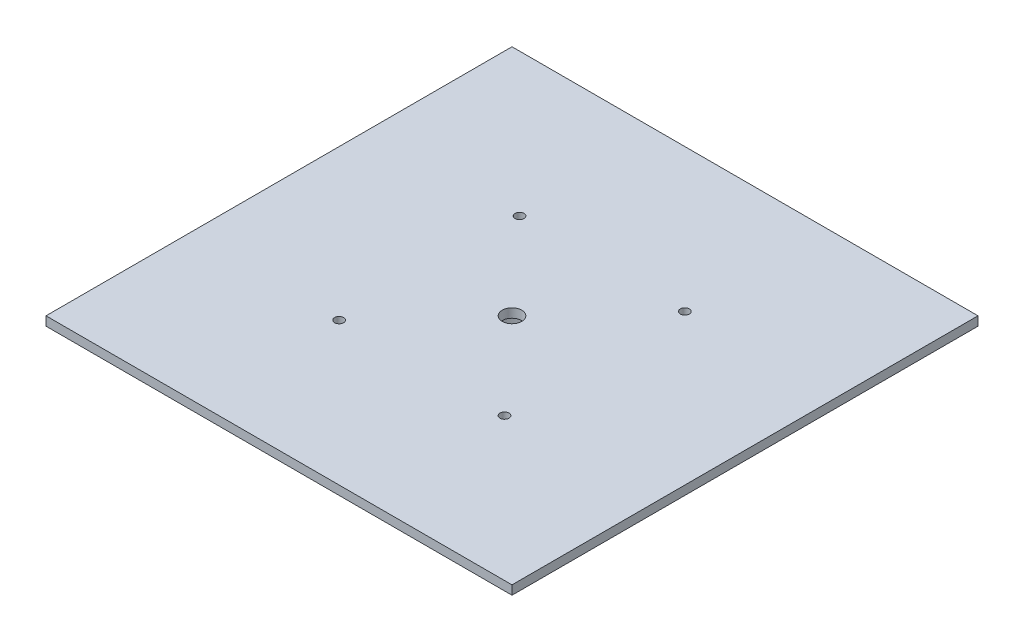
SolidWorks part; units mm, degrees
ref_plane "Front Plane" through (0, 0, 0) normal (0, 0, 1) x (1, 0, 0)
ref_plane "Top Plane" through (0, 0, 0) normal (0, 1, 0) x (1, 0, 0)
ref_plane "Right Plane" through (0, 0, 0) normal (1, 0, 0) x (0, 0, -1)
sketch "Sketch10" plane through (0, 0, 0) normal (0, -1, 0) x (1, 0, 0)
  line L0 (-67.8708, 79.6477) -> (-67.8708, 7.5) construction
  line L2 (-152.8708, -77.5) -> (-152.8708, 77.5)
  line L3 (-152.8708, 77.5) -> (2.1292, 77.5)
  line L4 (2.1292, -77.5) -> (2.1292, 77.5)
  line L5 (0, -55) -> (0, 55) construction
  line L7 (-67.8708, 7.5) -> (4.2768, 7.5) construction
  line L8 (-152.8708, -77.5) -> (2.1292, -77.5)
  line L9 (-82.8708, -79.6477) -> (-82.8708, -7.5) construction
  line L11 (55, 0) -> (-55, 0) construction
  point P22 (-75.3708, 0)
  dimension "D3" = 2.1292
  dimension "D1" = 155
  dimension "D2" = 155
  dimension "D4" = 77.5
extrude "Boss-Extrude3" add sketch "Sketch10" along normal blind 3
sketch "Sketch11" plane through (0, -3, 0) normal (0, -1, 0) x (1, 0, 0)
  line L0 (-152.8708, 77.5) -> (-135.2608, 77.5) construction
  line L1 (2.1292, 77.5) -> (-152.8708, 77.5) construction
  line L2 (-135.2608, 77.5) -> (-135.2608, 59.89) construction
  line L3 (-75.3708, -33.4232) -> (-75.3708, 33.4232) construction
  line L4 (1.65, 0) -> (-1.65, 0) construction
  line L5 (-152.8708, 77.5) -> (-152.8708, -77.5) construction
  circle A1 centre (-135.2608, 59.89) radius 2.3
  circle A2 centre (-15.4808, 59.89) radius 2.3
  circle A3 centre (-15.4808, -59.89) radius 2.3
  circle A4 centre (-135.2608, -59.89) radius 2.3
  circle A5 centre (-75.3708, 0) radius 17.5
  circle A6 centre (-75.3708, 0) radius 12.59
  point P13 (-75.3708, 0)
  dimension "D1" = 77.5
  dimension "D4" = 4.6
  dimension "D7" = 25.18
  dimension "D6" = 35
  dimension "D2" = 17.61
  dimension "D3" = 17.61
  dimension "D5" = 77.5
extrude "Boss-Extrude4" add sketch "Sketch11" along normal blind 8.4 contours A5 region at (-92.3759, -3, 0)
extrude "Boss-Extrude6" add sketch "Sketch11<4>" along normal blind 4 contours A1 | A2 | A4 | A3 region at (-135.2608, -3, 59.89) region at (-15.4808, -3, 59.89) region at (-15.4808, -3, -59.89) region at (-135.2608, -3, -59.89)
sketch "Sketch11<4>" plane through (0, -3, 0) normal (0, -1, 0) x (1, 0, 0) same geometry as "Sketch11"
sketch "Sketch12" plane through (0, 0, 0) normal (0, 0, 1) x (1, 0, 0)
  line L0 (-75.3708, -11.4) -> (-75.3708, -6.9) construction
  line L1 (-92.8708, -11.4) -> (-57.8708, -11.4) construction
  circle A0 centre (-75.3708, -6.9) radius 2.55
  dimension "D2" = 5.1
  dimension "D1" = 4.5
extrude "Cut-Extrude1" cut sketch "Sketch12" against normal blind 37
sketch "Sketch14" plane through (0, 0, 0) normal (1, 0, 0) x (0, 0, -1)
  line L0 (0, -11.4) -> (0, -6.9) construction
  line L1 (-17.5, -11.4) -> (17.5, -11.4) construction
  line L2 (0, 6.27) -> (0, -6.27) construction
  circle A0 centre (0, -6.9) radius 2.55
  dimension "D2" = 5.1
  dimension "D1" = 4.5
extrude "Cut-Extrude2" cut sketch "Sketch14" against normal blind 75
sketch "Sketch15" plane through (0, 0, 0) normal (0, 1, 0) x (1, 0, 0)
  line L0 (-6.27, 0) -> (6.27, 0) construction
  line L1 (-152.8708, -77.5) -> (-152.8708, 77.5) construction
  line L2 (-75.3708, -17.0682) -> (-75.3708, 17.0682) construction
  circle A0 centre (-102.8708, 30) radius 1.5
  circle A1 centre (-47.8708, 30) radius 1.5
  circle A2 centre (-47.8708, -30) radius 1.5
  circle A3 centre (-102.8708, -30) radius 1.5
  circle A4 centre (-75.3708, 0) radius 3.25
  point P9 (-75.3708, 0)
  point P14 (-75.3708, 0)
  dimension "D1" = 3
  dimension "D4" = 77.5
  dimension "D5" = 6.5
  dimension "D2" = 30
  dimension "D3" = 50
extrude "Cut-Extrude3" cut sketch "Sketch15" against normal blind 95
